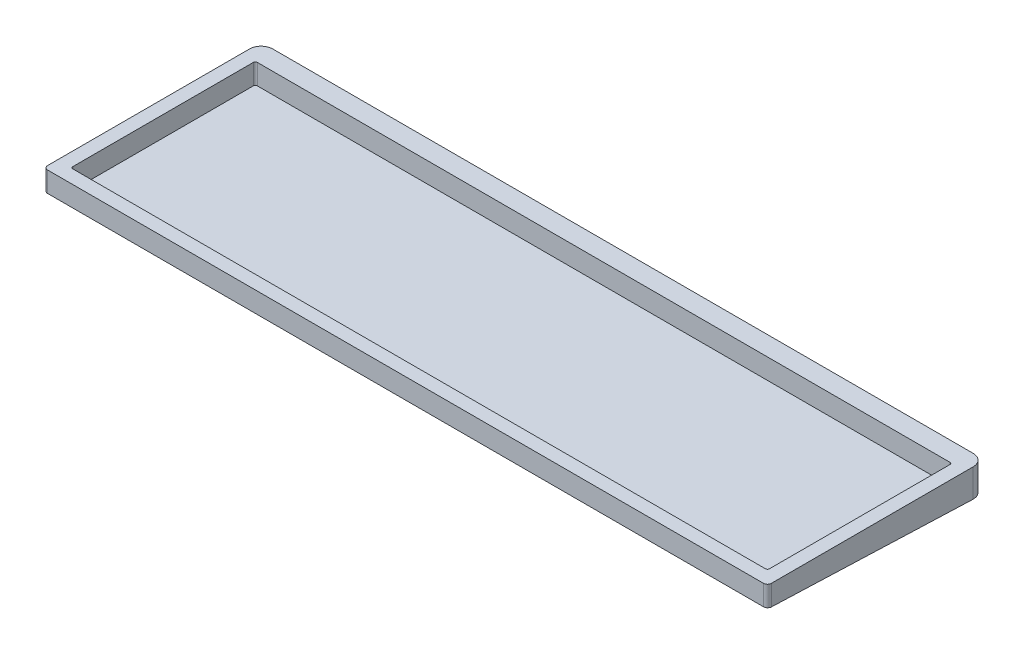
SolidWorks part; units mm, degrees
ref_plane "Front Plane" through (0, 0, 0) normal (0, 0, 1) x (1, 0, 0)
ref_plane "Top Plane" through (0, 0, 0) normal (0, 1, 0) x (1, 0, 0)
ref_plane "Right Plane" through (0, 0, 0) normal (1, 0, 0) x (0, 0, -1)
sketch "Sketch1" plane through (0, 0, 0) normal (0, 1, 0) x (1, 0, 0)
  line L1 (-178.825, 47.625) -> (178.825, 47.625)
  line L2 (-179.825, 46.625) -> (-179.825, -46.625)
  line L3 (-178.825, -47.625) -> (178.825, -47.625)
  line L4 (179.825, 46.625) -> (179.825, -46.625)
  line L5 (-179.825, 47.625) -> (179.825, -47.625) construction
  line L6 (-179.825, -47.625) -> (179.825, 47.625) construction
  arc A0 (178.825, -47.625) -> (179.825, -46.625) centre (178.825, -46.625) ccw
  arc A1 (178.825, 47.625) -> (179.825, 46.625) centre (178.825, 46.625) cw
  arc A2 (-179.825, -46.625) -> (-178.825, -47.625) centre (-178.825, -46.625) ccw
  arc A3 (-178.825, 47.625) -> (-179.825, 46.625) centre (-178.825, 46.625) ccw
  circle A4 centre (157.075, 19.175) radius 1.1
  circle A5 centre (136.925, -16.775) radius 1.1
  circle A6 centre (-153.475, 33.725) radius 1.1
  circle A7 centre (17.925, 22.275) radius 1.1
  circle A8 centre (17.875, -35.075) radius 1.1
  circle A9 centre (-130.375, -35.725) radius 1.1
  point P0 (0, 0)
  dimension "D3" = 1
  dimension "D4" = 2.2
  dimension "D7" = 2.2
  dimension "D8" = 2.2
  dimension "D9" = 2.2
  dimension "D10" = 2.2
  dimension "D11" = 2.2
  dimension "D1" = 359.65
  dimension "D2" = 95.25
  dimension "D5" = 22.75
  dimension "D6" = 28.45
  dimension "D12" = 42.9
  dimension "D13" = 30.85
  dimension "D14" = 25.35
  dimension "D15" = 161.9
  dimension "D16" = 12.55
  dimension "D17" = 161.95
  dimension "D18" = 11.9
  dimension "D19" = 49.45
  dimension "D20" = 13.9
  dimension "D21" = 26.35
sketch "Sketch2" plane through (0, 0, 0) normal (0, 1, 0) x (1, 0, 0)
  line L0 (-179.825, 46.625) -> (-179.825, -46.625) construction
  line L1 (-178.825, -47.625) -> (178.825, -47.625) construction
  line L2 (179.825, 46.625) -> (179.825, -46.625) construction
  line L3 (-178.825, 47.625) -> (178.825, 47.625) construction
  line L4 (-179.825, 46.625) -> (-179.825, -46.625)
  line L5 (-178.825, -47.625) -> (178.825, -47.625)
  line L6 (179.825, 46.625) -> (179.825, -46.625)
  line L7 (-178.825, 47.625) -> (178.825, 47.625)
  line L9 (-180.825, 57.625) -> (180.825, 57.625)
  line L10 (-186.825, 51.625) -> (-186.825, -52.625)
  line L11 (-184.825, -54.625) -> (184.825, -54.625)
  line L12 (186.825, 51.625) -> (186.825, -52.625)
  circle A0 centre (157.075, 19.175) radius 1.1 construction
  circle A1 centre (136.925, -16.775) radius 1.1 construction
  circle A2 centre (17.875, -35.075) radius 1.1 construction
  circle A3 centre (17.925, 22.275) radius 1.1 construction
  circle A4 centre (-153.475, 33.725) radius 1.1 construction
  circle A5 centre (-130.375, -35.725) radius 1.1 construction
  arc A6 (-179.825, -46.625) -> (-178.825, -47.625) centre (-178.825, -46.625) ccw construction
  arc A7 (178.825, -47.625) -> (179.825, -46.625) centre (178.825, -46.625) ccw construction
  arc A8 (179.825, 46.625) -> (178.825, 47.625) centre (178.825, 46.625) ccw construction
  arc A9 (-178.825, 47.625) -> (-179.825, 46.625) centre (-178.825, 46.625) ccw construction
  circle A10 centre (157.075, 19.175) radius 1.1
  circle A11 centre (136.925, -16.775) radius 1.1
  circle A12 centre (17.875, -35.075) radius 1.1
  circle A13 centre (17.925, 22.275) radius 1.1
  circle A14 centre (-153.475, 33.725) radius 1.1
  circle A15 centre (-130.375, -35.725) radius 1.1
  arc A16 (-179.825, -46.625) -> (-178.825, -47.625) centre (-178.825, -46.625) ccw
  arc A17 (178.825, -47.625) -> (179.825, -46.625) centre (178.825, -46.625) ccw
  arc A18 (179.825, 46.625) -> (178.825, 47.625) centre (178.825, 46.625) ccw
  arc A19 (-178.825, 47.625) -> (-179.825, 46.625) centre (-178.825, 46.625) ccw
  arc A20 (180.825, 57.625) -> (186.825, 51.625) centre (180.825, 51.625) cw
  arc A21 (-180.825, 57.625) -> (-186.825, 51.625) centre (-180.825, 51.625) ccw
  arc A22 (184.825, -54.625) -> (186.825, -52.625) centre (184.825, -52.625) ccw
  arc A23 (-186.825, -52.625) -> (-184.825, -54.625) centre (-184.825, -52.625) ccw
  point P30 (0, 0)
  dimension "D5" = 6
  dimension "D6" = 2
  dimension "D1" = 10
  dimension "D2" = 7
  dimension "D3" = 7
  dimension "D4" = 7
extrude "Boss-Extrude1" add sketch "Sketch2" along normal blind 10.5 contours L10 A23 L11 A22 L12 A20 L9 A21 A19 L7 A18 L6 A17 L5 A16 L4 region at (0, 0, -53.7235)
sketch "Sketch4" plane through (0, 0, 0) normal (0, -1, 0) x (1, 0, 0)
  line L0 (186.825, -51.625) -> (186.825, 52.625) construction
  line L1 (-180.825, -57.625) -> (180.825, -57.625) construction
  line L2 (-186.825, -51.625) -> (-186.825, 52.625) construction
  line L3 (-184.825, 54.625) -> (184.825, 54.625) construction
  line L4 (-179.825, 46.625) -> (-179.825, -46.625)
  line L5 (178.825, 47.625) -> (-178.825, 47.625)
  line L6 (179.825, -46.625) -> (179.825, 46.625)
  line L7 (-178.825, -47.625) -> (178.825, -47.625)
  line L8 (-179.825, 46.625) -> (-179.825, -46.625)
  line L10 (179.825, -46.625) -> (179.825, 46.625)
  line L11 (-178.825, -47.625) -> (178.825, -47.625)
  line L12 (186.825, -51.625) -> (186.825, 52.625)
  line L13 (-180.825, -57.625) -> (180.825, -57.625)
  line L14 (-186.825, -51.625) -> (-186.825, 52.625)
  line L15 (-184.825, 54.625) -> (184.825, 54.625)
  arc A0 (186.825, 52.625) -> (184.825, 54.625) centre (184.825, 52.625) ccw construction
  arc A1 (180.825, -57.625) -> (186.825, -51.625) centre (180.825, -51.625) ccw construction
  arc A2 (-186.825, -51.625) -> (-180.825, -57.625) centre (-180.825, -51.625) ccw construction
  arc A3 (-184.825, 54.625) -> (-186.825, 52.625) centre (-184.825, 52.625) ccw construction
  arc A4 (-179.825, -46.625) -> (-178.825, -47.625) centre (-178.825, -46.625) ccw
  arc A5 (-178.825, 47.625) -> (-179.825, 46.625) centre (-178.825, 46.625) ccw
  arc A6 (179.825, 46.625) -> (178.825, 47.625) centre (178.825, 46.625) ccw
  arc A7 (178.825, -47.625) -> (179.825, -46.625) centre (178.825, -46.625) ccw
  arc A8 (-179.825, -46.625) -> (-178.825, -47.625) centre (-178.825, -46.625) ccw
  arc A9 (-178.825, 47.625) -> (-179.825, 46.625) centre (-178.825, 46.625) ccw
  arc A10 (179.825, 46.625) -> (178.825, 47.625) centre (178.825, 46.625) ccw
  arc A11 (178.825, -47.625) -> (179.825, -46.625) centre (178.825, -46.625) ccw
  arc A12 (186.825, 52.625) -> (184.825, 54.625) centre (184.825, 52.625) ccw
  arc A13 (180.825, -57.625) -> (186.825, -51.625) centre (180.825, -51.625) ccw
  arc A14 (-186.825, -51.625) -> (-180.825, -57.625) centre (-180.825, -51.625) ccw
  arc A15 (-184.825, 54.625) -> (-186.825, 52.625) centre (-184.825, 52.625) ccw
  arc M9 (-178.825, -47.625) -> (-179.825, -46.625) centre (-178.825, -46.625) cw
  line M10 (-179.825, -46.625) -> (-179.825, 46.625)
  arc M11 (-179.825, 46.625) -> (-178.825, 47.625) centre (-178.825, 46.625) cw
  line M12 (-178.825, 47.625) -> (178.825, 47.625)
  arc M13 (178.825, 47.625) -> (179.825, 46.625) centre (178.825, 46.625) cw
  line M14 (179.825, 46.625) -> (179.825, -46.625)
  arc M15 (179.825, -46.625) -> (178.825, -47.625) centre (178.825, -46.625) cw
  line M16 (178.825, -47.625) -> (-178.825, -47.625)
  line M17 (-186.825, 52.625) -> (-186.825, -51.625)
  arc M18 (-186.825, -51.625) -> (-180.825, -57.625) centre (-180.825, -51.625) ccw
  line M19 (-180.825, -57.625) -> (180.825, -57.625)
  arc M20 (180.825, -57.625) -> (186.825, -51.625) centre (180.825, -51.625) ccw
  line M21 (186.825, -51.625) -> (186.825, 52.625)
  arc M22 (186.825, 52.625) -> (184.825, 54.625) centre (184.825, 52.625) ccw
  line M23 (184.825, 54.625) -> (-184.825, 54.625)
  arc M24 (-184.825, 54.625) -> (-186.825, 52.625) centre (-184.825, 52.625) ccw
  dimension "D1" = 0
extrude "Boss-Extrude3" add sketch "Sketch4" along normal blind 10.5 contours M24 M17 M18 M19 M20 M21 M22 M23 M16 M9 M10 M11 M12 M13 M14 M15 | M9 M16 M15 M14 M13 M12 M11 M10 region at (0, 0, 0) region at (182.3089, 0, -53.1089)
sketch "Sketch5" plane through (186.825, 0, 0) normal (1, 0, 0) x (0, 0, -1)
  line L0 (-54.625, 0) -> (57.625, 0) construction
  line L1 (-54.625, 10.5) -> (-54.625, -10.5) construction
  line L2 (57.625, 10.5) -> (57.625, -10.5) construction
  line L4 (57.625, -4) -> (51.625, -4)
  line L14 (40.9479, -10.5) -> (-54.625, 0)
  line L17 (-54.625, 0) -> (-54.625, -10.5)
  line L18 (-54.625, -10.5) -> (40.9479, -10.5)
  line L21 (51.625, -10.5) -> (-52.625, -10.5) construction
  line L22 (51.625, -10.5) -> (40.9479, -10.5)
  line L23 (51.625, 10.5) -> (51.625, -10.5) construction
  line L24 (51.625, -4) -> (40.9479, -10.5)
  line L25 (40.9479, -10.5) -> (57.625, -10.5)
  line L26 (57.625, -10.5) -> (57.625, -4)
  line M5 (-52.625, 10.5) -> (-52.625, -10.5)
  line M6 (-52.625, -10.5) -> (51.625, -10.5)
  line M7 (51.625, -10.5) -> (51.625, 10.5)
  dimension "D1" = 4
  dimension "D2" = 12.5
extrude "Cut-Extrude1" cut sketch "Sketch5" against normal blind 400 contours L17 L18 L14 M5 | L14 M6 M5 | L24 M7 M6 | L25 L26 L4 M7 region at (186.825, -7.25, -54.625) region at (186.825, -7.0732, 21.434) region at (186.825, -8.3333, -48.066) region at (186.825, -5.3047, 53.6285)
sketch "Sketch6" plane through (186.825, 0, 0) normal (1, 0, 0) x (0, 0, -1)
  line L4 (-54.625, 0) -> (51.625, -4)
  line L5 (51.625, -4) -> (40.9479, -10.5)
  line L6 (40.9479, -10.5) -> (-54.625, 0)
extrude "Cut-Extrude2" cut sketch "Sketch6" against normal blind 40
sketch "Sketch7" plane through (-186.825, 0, 0) normal (-1, 0, 0) x (0, 0, 1)
  line L4 (-51.625, -4) -> (-40.9479, -10.5)
  line L5 (-40.9479, -10.5) -> (52.625, -0.2197)
  line L6 (52.625, -0.2197) -> (-51.625, -4)
extrude "Cut-Extrude3" cut sketch "Sketch7" against normal blind 40
ref_plane "Plane1" through (0, -10.5, 0) normal (0, 1, 0) x (1, 0, 0)
